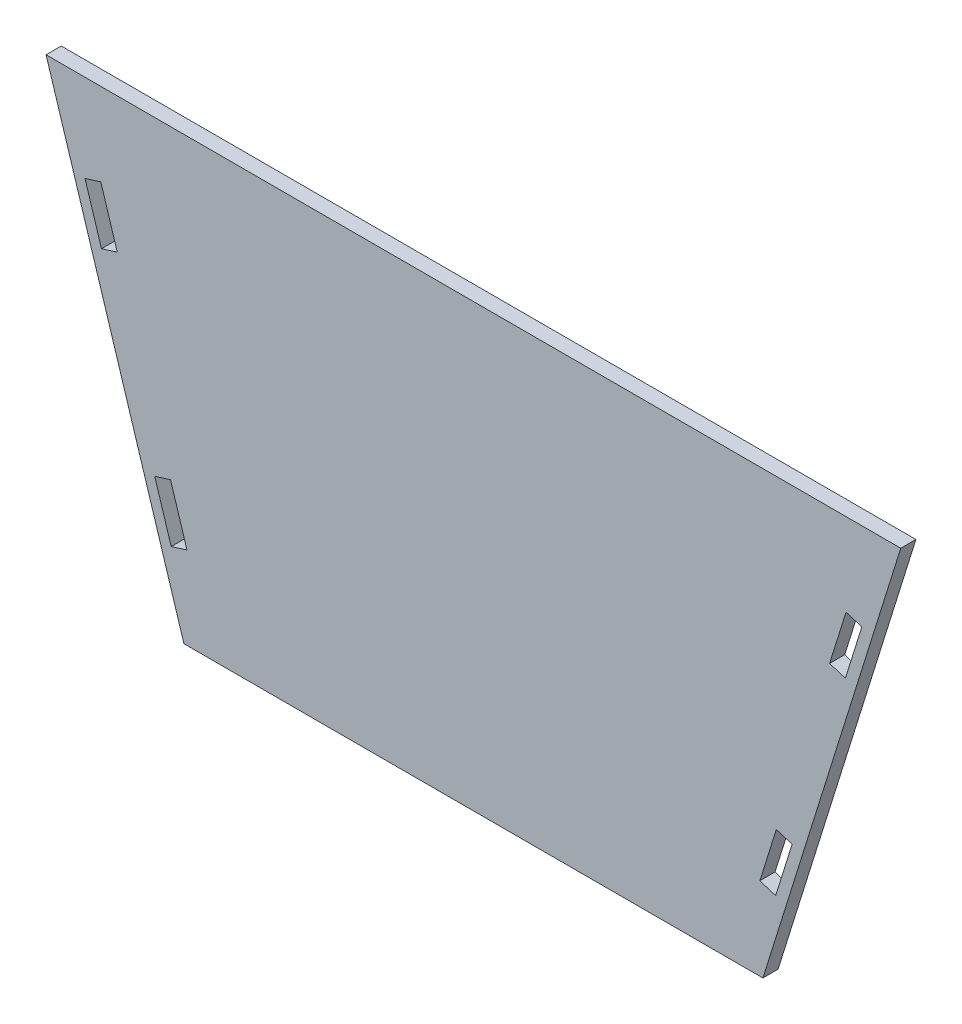
SolidWorks part; units mm, degrees
ref_plane "Front Plane" through (0, 0, 0) normal (0, 0, 1) x (1, 0, 0)
ref_plane "Top Plane" through (0, 0, 0) normal (0, 1, 0) x (1, 0, 0)
ref_plane "Right Plane" through (0, 0, 0) normal (1, 0, 0) x (0, 0, -1)
sketch "Sketch1" plane through (0, 0, 0) normal (0, 0, 1) x (1, 0, 0)
  line L0 (-52.5, 0) -> (52.5, 0)
  line L1 (55, 0) -> (-55, 0) construction
  line L2 (52.5, 0) -> (77.5, 80)
  line L3 (77.5, 80) -> (-77.5, 80)
  line L4 (0, -55) -> (0, 55) construction
  line L5 (-52.5, 0) -> (-77.5, 80)
  point P10 (0, 80)
  point P11 (0, 0)
  dimension "D1" = 105
  dimension "D2" = 25
  dimension "D3" = 80
extrude "Boss-Extrude1" add sketch "Sketch1" along normal blind 2.75
ref_axis "Axis1" through (52.5, 0, 2.75) along (0.2983, 0.9545, 0)
sketch "Sketch4" plane through (0, 0, 2.75) normal (0, 0, 1) x (1, 0, 0)
  line L0 (70.4375, 64.1052) -> (67.4547, 54.5604)
  line L1 (70.4375, 64.1052) -> (67.574, 65)
  line L2 (67.4547, 54.5604) -> (64.5913, 55.4552)
  line L3 (67.574, 65) -> (64.5913, 55.4552)
  line L4 (77.5, 80) -> (-77.5, 80) construction
  line L5 (52.5, 0) -> (77.5, 80) construction
  line L6 (57.7952, 23.65) -> (54.8125, 14.1052)
  line L7 (57.7952, 23.65) -> (54.9318, 24.5448)
  line L8 (54.8125, 14.1052) -> (51.949, 15)
  line L9 (54.9318, 24.5448) -> (51.949, 15)
  line L10 (55, 0) -> (-55, 0) construction
  line L11 (0, -55) -> (0, 55) construction
  line L12 (-54.9318, 24.5448) -> (-51.949, 15)
  line L13 (-54.8125, 14.1052) -> (-51.949, 15)
  line L14 (-57.7952, 23.65) -> (-54.9318, 24.5448)
  line L15 (-57.7952, 23.65) -> (-54.8125, 14.1052)
  line L16 (-67.574, 65) -> (-64.5913, 55.4552)
  line L17 (-67.4547, 54.5604) -> (-64.5913, 55.4552)
  line L18 (-70.4375, 64.1052) -> (-67.574, 65)
  line L19 (-70.4375, 64.1052) -> (-67.4547, 54.5604)
  point P6 (68.9461, 59.3328)
  dimension "D1" = 2
  dimension "D2" = 10
  dimension "D3" = 3
  dimension "D4" = 15
  dimension "D5" = 10
  dimension "D6" = 3
  dimension "D7" = 2
  dimension "D8" = 15
extrude "Cut-Extrude1" cut sketch "Sketch4" against normal blind 10
